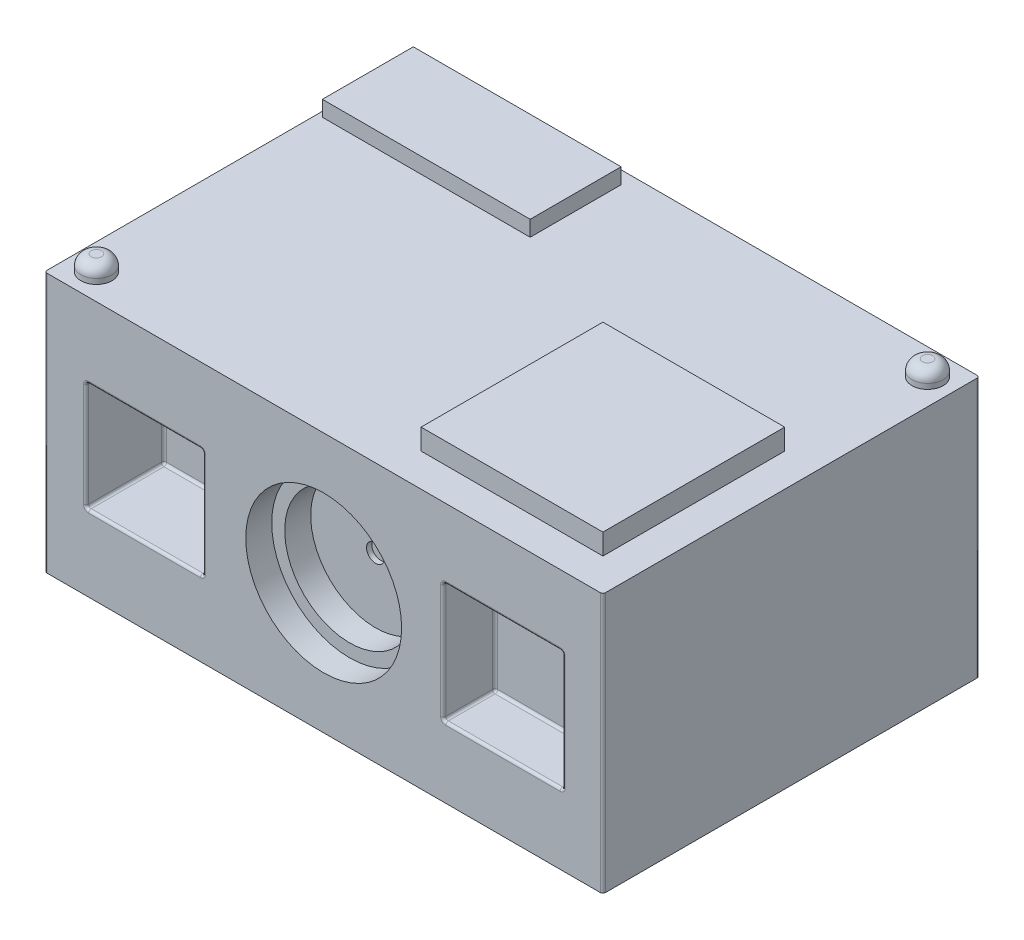
SolidWorks part; units mm, degrees
ref_plane "前视基准面" through (0, 0, 0) normal (0, 0, 1) x (1, 0, 0)
ref_plane "上视基准面" through (0, 0, 0) normal (0, 1, 0) x (1, 0, 0)
ref_plane "右视基准面" through (0, 0, 0) normal (1, 0, 0) x (0, 0, -1)
sketch "草图1" plane through (0, 0, 0) normal (0, 1, 0) x (1, 0, 0)
  line L1 (-10.75, 7.25) -> (10.75, 7.25)
  line L2 (-10.75, 7.25) -> (-10.75, -7.25)
  line L3 (-10.75, -7.25) -> (10.75, -7.25)
  line L4 (10.75, 7.25) -> (10.75, -7.25)
  line L5 (-10.75, 7.25) -> (10.75, -7.25) construction
  line L6 (-10.75, -7.25) -> (10.75, 7.25) construction
  point P0 (0, 0)
  dimension "D1" = 21.5
  dimension "D2" = 14.5
extrude "凸台-拉伸1" add sketch "草图1" along normal blind 10 contours L1 L4 L3 L2
sketch "草图2" plane through (0, 0, 7.25) normal (0, 0, 1) x (1, 0, 0)
  line L0 (-10.75, 10) -> (-10.75, 0) construction
  line L1 (-9.15, 7.1) -> (-4.65, 7.1)
  line L2 (-9.15, 7.1) -> (-9.15, 2.9)
  line L3 (-9.15, 2.9) -> (-4.65, 2.9)
  line L4 (-4.65, 7.1) -> (-4.65, 2.9)
  line L5 (-9.15, 7.1) -> (-4.65, 2.9) construction
  line L6 (-9.15, 2.9) -> (-4.65, 7.1) construction
  line L7 (4.6, 7.3) -> (9.2, 7.3)
  line L8 (4.6, 7.3) -> (4.6, 2.7)
  line L9 (4.6, 2.7) -> (9.2, 2.7)
  line L10 (9.2, 7.3) -> (9.2, 2.7)
  line L11 (4.6, 7.3) -> (9.2, 2.7) construction
  line L12 (4.6, 2.7) -> (9.2, 7.3) construction
  circle A0 centre (0, 5) radius 2.5
  circle A1 centre (0, 5) radius 3
  point P3 (6.9, 5)
  point P4 (-6.9, 5)
  point P16 (-10.75, 5)
  dimension "D1" = 5
  dimension "D2" = 6
  dimension "D3" = 6.9
  dimension "D4" = 6.9
  dimension "D5" = 4.5
  dimension "D6" = 4.2
  dimension "D7" = 4.6
  dimension "D8" = 4.6
extrude "切除-拉伸1" cut sketch "草图2" against normal blind 3 contours L4 L1 L2 L3 region at (-6.9, 5, 7.25)
extrude "切除-拉伸2" cut sketch "草图2<3>" against normal blind 2 contours A0 | L8 L7 L10 L9 region at (0, 5, 7.25)
sketch "草图2<3>" plane through (0, 0, 7.25) normal (0, 0, 1) x (1, 0, 0) same geometry as "草图2"
extrude "切除-拉伸3" cut sketch "草图2<4>" against normal blind 1 contours A1 A0 region at (-2.9151, 5, 7.25)
sketch "草图2<4>" plane through (0, 0, 7.25) normal (0, 0, 1) x (1, 0, 0) same geometry as "草图2"
sketch "草图3" plane through (0, 10, 0) normal (0, 1, 0) x (1, 0, 0)
  line L0 (-10.75, -7.25) -> (10.75, -7.25) construction
  line L1 (2.48, 1.02) -> (9.48, 1.02)
  line L2 (2.48, 1.02) -> (2.48, -5.98)
  line L3 (2.48, -5.98) -> (9.48, -5.98)
  line L4 (9.48, 1.02) -> (9.48, -5.98)
  line L5 (2.48, 1.02) -> (9.48, -5.98) construction
  line L6 (2.48, -5.98) -> (9.48, 1.02) construction
  line L7 (10.75, 7.25) -> (10.75, -7.25) construction
  point P0 (5.98, -2.48)
  dimension "D1" = 1.27
  dimension "D2" = 1.27
  dimension "D3" = 7
  dimension "D4" = 7
sketch "草图4" plane through (0, 10, 0) normal (0, 1, 0) x (1, 0, 0)
  line L0 (10.75, 7.25) -> (10.75, -7.25) construction
  line L1 (-10.75, 7.25) -> (10.75, 7.25) construction
  line L2 (-10.75, -7.25) -> (10.75, -7.25) construction
  line L3 (-10.75, 7.25) -> (-10.75, -7.25) construction
  line L9 (-10.55, 6.75) -> (-2.55, 6.75)
  line L10 (-10.55, 6.75) -> (-10.55, 3.25)
  line L15 (-10.55, 3.25) -> (-2.55, 3.25)
  line L16 (-2.55, 6.75) -> (-2.55, 3.25)
  line L17 (-10.55, 6.75) -> (-2.55, 3.25) construction
  line L18 (-10.55, 3.25) -> (-2.55, 6.75) construction
  circle A0 centre (-9.75, -6.25) radius 0.6
  circle A1 centre (9.75, 6.25) radius 0.6
  point P4 (-6.55, 5)
  dimension "D1" = 1.2
  dimension "D2" = 1.2
  dimension "D6" = 1
  dimension "D3" = 1
  dimension "D4" = 1
  dimension "D5" = 1
  dimension "D7" = 3.5
  dimension "D8" = 8
  dimension "D9" = 0.5
  dimension "D10" = 0.2
extrude "凸台-拉伸2" add sketch "草图3" along normal blind 0.8
extrude "凸台-拉伸3" add sketch "草图4" along normal blind 0.6
fillet "圆角1" radius 0.4 2 edges at (9.75, 10.6, -5.65) (-9.75, 10.6, 6.85)
sketch "草图5" plane through (0, 0, 5.25) normal (0, 0, 1) x (1, 0, 0)
  circle A0 centre (0, 5) radius 0.35
  dimension "D1" = 0.7
extrude "切除-拉伸4" cut sketch "草图5" against normal blind 0.2 contours A0
fillet "圆角2" radius 0.1 28 edges at (-6.9, 2.9, 7.25) (6.9, 2.7, 7.25) (-9.15, 5, 7.25) (-4.65, 5, 7.25) (4.6, 5, 7.25) (9.2, 5, 7.25) (4.6, 5, 5.25) (6.9, 7.3, 5.25) (9.2, 5, 5.25) (6.9, 2.7, 5.25) (-6.9, 2.9, 4.25) (-9.15, 5, 4.25) (-6.9, 7.1, 4.25) (-4.65, 5, 4.25) (-6.9, 7.1, 7.25) (6.9, 7.3, 7.25) (9.2, 2.7, 6.25) (4.6, 2.7, 6.25) (9.2, 7.3, 6.25) (4.6, 7.3, 6.25) (-4.65, 2.9, 5.75) (-9.15, 2.9, 5.75) (-9.15, 7.1, 5.75) (-4.65, 7.1, 5.75) (-10.75, 5, 7.25) (-10.75, 5, -7.25) (10.75, 5, -7.25) (10.75, 5, 7.25)
